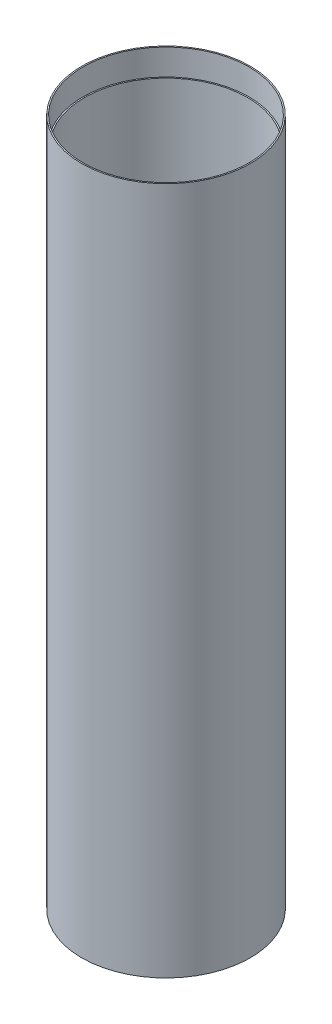
SolidWorks part; units mm, degrees
material "HYPALON"
ref_plane "Płaszczyzna przednia" through (0, 0, 0) normal (0, 0, 1) x (1, 0, 0)
ref_plane "Płaszczyzna górna" through (0, 0, 0) normal (0, 1, 0) x (1, 0, 0)
ref_plane "Płaszczyzna prawa" through (0, 0, 0) normal (1, 0, 0) x (0, 0, -1)
sketch "Szkic1" plane through (0, 0, 0) normal (0, 0, 1) x (1, 0, 0)
  line L0 (64, 265) -> (65, 265)
  line L1 (65, 265) -> (65, -265)
  line L2 (65, -265) -> (64, -265)
  line L3 (64, -265) -> (64, -245)
  line L4 (64, -245) -> (63, -245)
  line L5 (63, -245) -> (63, 245)
  line L6 (63, 245) -> (64, 245)
  line L7 (64, 245) -> (64, 265)
  line L8 (0, 0) -> (0, 92.2309) construction
  point P2 (63, 0)
  dimension "D1" = 530
  dimension "D2" = 20
  dimension "D3" = 20
  dimension "D4" = 2
  dimension "D5" = 63
  dimension "3" = 1
revolve "Obrót1" add sketch "Szkic1" angle 360 about L8
